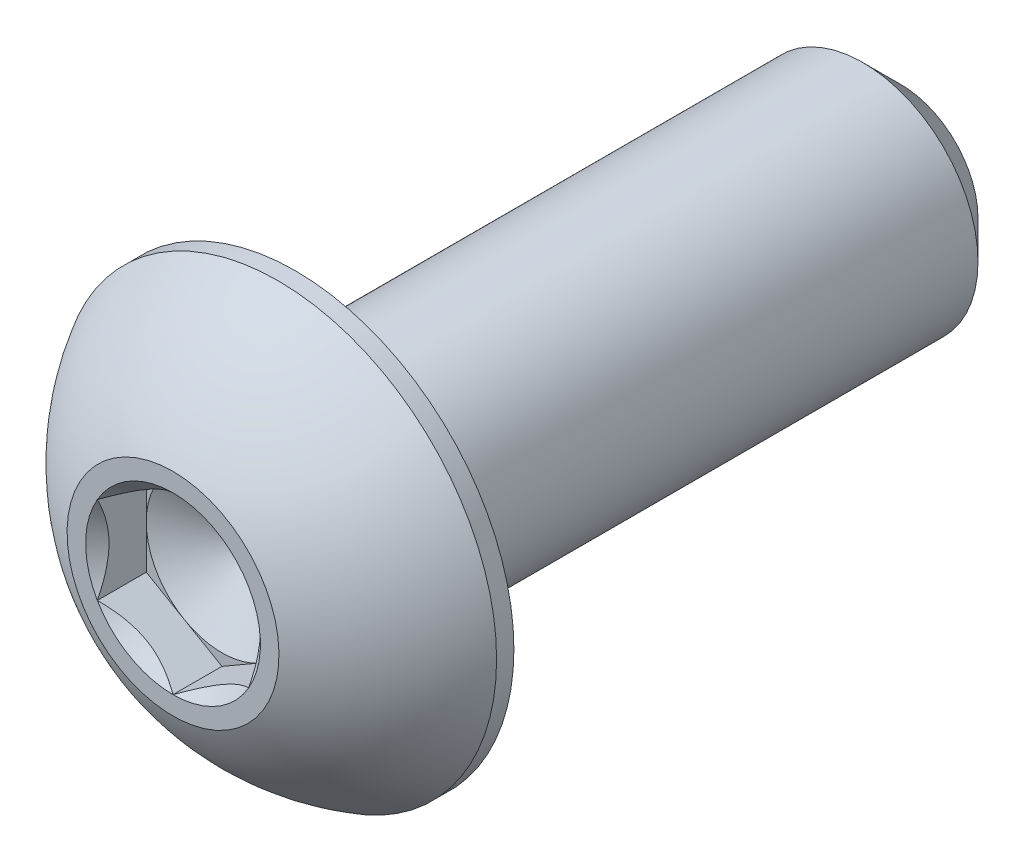
SolidWorks part; units mm, degrees
ref_plane "Front Plane" through (0, 0, 0) normal (0, 0, 1) x (1, 0, 0)
ref_plane "Top Plane" through (0, 0, 0) normal (0, 1, 0) x (1, 0, 0)
ref_plane "Right Plane" through (0, 0, 0) normal (1, 0, 0) x (0, 0, -1)
sketch "Sketch1" plane through (0, 0, 0) normal (1, 0, 0) x (0, 0, -1)
  line L0 (-7.6327, 0) -> (7.6327, 0) construction
  line L1 (-5.0673, 4.5847) -> (-5.0673, -4.5847) construction
  line L2 (-7.6327, 1.5875) -> (-7.6327, -1.5875) construction
  line L3 (7.6327, 2.413) -> (7.6327, -2.413) construction
  line L4 (7.5666, 2.5276) -> (8.0957, 1.611) construction
  line L5 (8.0957, 1.611) -> (8.6249, 2.5276) construction
  line L6 (8.6249, 2.5276) -> (7.5666, 2.5276) construction
  line L7 (8.0957, 2.5276) -> (8.0957, 2.413) construction
  line L8 (8.0957, 1.611) -> (8.0957, 1.7256) construction
  line L9 (8.0296, 1.7256) -> (8.1619, 1.7256)
  line L10 (-7.6327, 2.2225) -> (-7.6327, -2.2225) construction
  line L11 (-5.0673, 4.5847) -> (-5.4302, 4.5847) construction
  line L12 (-7.6327, 1.5875) -> (-6.6065, 1.5875) construction
  line L13 (-6.6065, 1.5875) -> (-5.69, 0) construction
  point P5 (-5.0673, 0)
  point P10 (3.9285, -2.413)
  dimension "Drive Size" = 3.175
  dimension "Head Diameter" = 9.1694
  dimension "Head Height" = 2.5654
  dimension "Diameter" = 4.826
  dimension "Thread Length" = 12.7
  dimension "D1" = 3.7042
  dimension "Pitch" = 1.0583
  dimension "D2" = 0.1323
  dimension "D3" = 4.445
  dimension "D4" = 0.3629
  dimension "D5" = 60
  dimension "D6" = 1.0262
sketch "Sketch2" plane through (0, 0, 0) normal (1, 0, 0) x (0, 0, -1)
  line L0 (-7.6327, 1.5875) -> (-7.6327, 2.2225)
  line L1 (-5.4302, 4.5847) -> (-5.0673, 4.5847)
  line L2 (-5.0673, 4.5847) -> (-5.0673, 2.413)
  line L3 (-5.0673, 4.5847) -> (-5.0673, -4.5847) construction
  line L4 (-5.0673, 2.413) -> (6.8389, 2.413)
  line L5 (7.6327, 1.6193) -> (7.6327, 0)
  line L6 (-7.6327, 1.5875) -> (-6.6065, 1.5875)
  line L7 (-6.6065, 1.5875) -> (-5.69, 0)
  line L8 (7.6327, 0) -> (-5.69, 0)
  line L9 (6.8389, 2.413) -> (7.6327, 1.6193)
  arc A0 (-5.4302, 4.5847) -> (-7.6327, 2.2225) centre (-2.8811, 0) ccw
  point P13 (7.6327, 2.413)
  dimension "D1" = 0.7937
  dimension "D2" = 45
revolve "Revolve1" add sketch "Sketch2" angle 360 about L0
sketch "Sketch3" plane through (0, 0, 0) normal (0, 0, 1) x (1, 0, 0)
  line L1 (0, 1.8331) -> (-1.5875, 0.9165)
  line L2 (-1.5875, 0.9165) -> (-1.5875, -0.9165)
  line L3 (-1.5875, -0.9165) -> (0, -1.8331)
  line L4 (0, -1.8331) -> (1.5875, -0.9165)
  line L5 (1.5875, -0.9165) -> (1.5875, 0.9165)
  line L6 (1.5875, 0.9165) -> (0, 1.8331)
  circle A0 centre (0, 0) radius 1.5875 construction
extrude "Cut-Extrude1" cut sketch "Sketch3" along normal through all from vertex starting at point (0, 1.5875, 6.6065)
sketch "Sketch4" plane through (0, 0, 7.6327) normal (0, 0, 1) x (1, 0, 0)
  circle A0 centre (0, 0) radius 1.8331
extrude "Cut-Extrude2" cut sketch "Sketch4" against normal up to next (1.9427 mm away) draft 45
sketch "Sketch5" plane through (0, 0, -7.6327) normal (0, 0, -1) x (-1, 0, 0)
  circle A0 centre (0, 0) radius 2.413
curve "Helix/Spiral1" [suppressed] pitch 1.0583 height 13.7583 turns 13
sketch "Sketch6" plane through (0, 0, 0) normal (1, 0, 0) x (0, 0, -1)
  line L0 (7.6327, 2.413) -> (8.5587, 2.413)
  line L1 (8.5587, 2.413) -> (8.1619, 1.7256)
  line L2 (8.0296, 1.7256) -> (8.1619, 1.7256)
  line L3 (8.0296, 1.7256) -> (7.6327, 2.413)
  line L4 (8.0957, 1.611) -> (8.6249, 2.5276) construction
sweep "Sweep1" [suppressed] add profiles "Sketch6" path "Helix/Spiral1"
combine bodies "Combine1" [suppressed] operation type subtract main body 104 bodies to subtract 105
sketch "Sketch7" plane through (0, 0, 0) normal (1, 0, 0) x (0, 0, -1)
  line L0 (-6.6065, 2.413) -> (-5.0673, 2.413)
  line L1 (-6.6065, 2.413) -> (-6.6065, 1.5875)
  line L2 (-6.6065, 1.5875) -> (-5.69, 0)
  line L3 (-5.69, 0) -> (-2.8639, 0)
  line L5 (-5.0673, 4.5847) -> (-5.0673, -4.5847) construction
  line L6 (-5.0673, 2.413) -> (-2.8639, 1.611)
  line L7 (-2.8639, 1.611) -> (-2.8639, 0)
  dimension "D1" = 20
revolve "Revolve2" [suppressed] add sketch "Sketch7" angle 360 about L0
ref_axis "Center Axis 1" through (0, 0, -4.0714) along (0, 0, 1)
ref_plane "Contact Plane 1" through (0, 0, 5.0673) normal (0, 0, -1) x (-1, 0, 0)
equation "\"D2@Sketch1\"=\"Pitch@Sketch1\"*.125"
equation "\"D1@Sketch1\"=\"Pitch@Sketch1\"*3.5"
equation "\"D3@Sketch1\"=\"Drive Size@Sketch1\"*1.4"
equation "\"D4@Sketch1\"=(\"D3@Sketch1\"-\"Drive Size@Sketch1\")/3.5"
equation "\"D6@Sketch1\"=\"Head Height@Sketch1\"*.40"
equation "\"D1@Sketch2\"=\"Pitch@Sketch1\"*.750"
equation "\"D4@Helix/Spiral1\"=\"Pitch@Sketch1\""
equation "\"D3@Helix/Spiral1\"=\"D4@Helix/Spiral1\"+\"Thread Length@Sketch1\""
